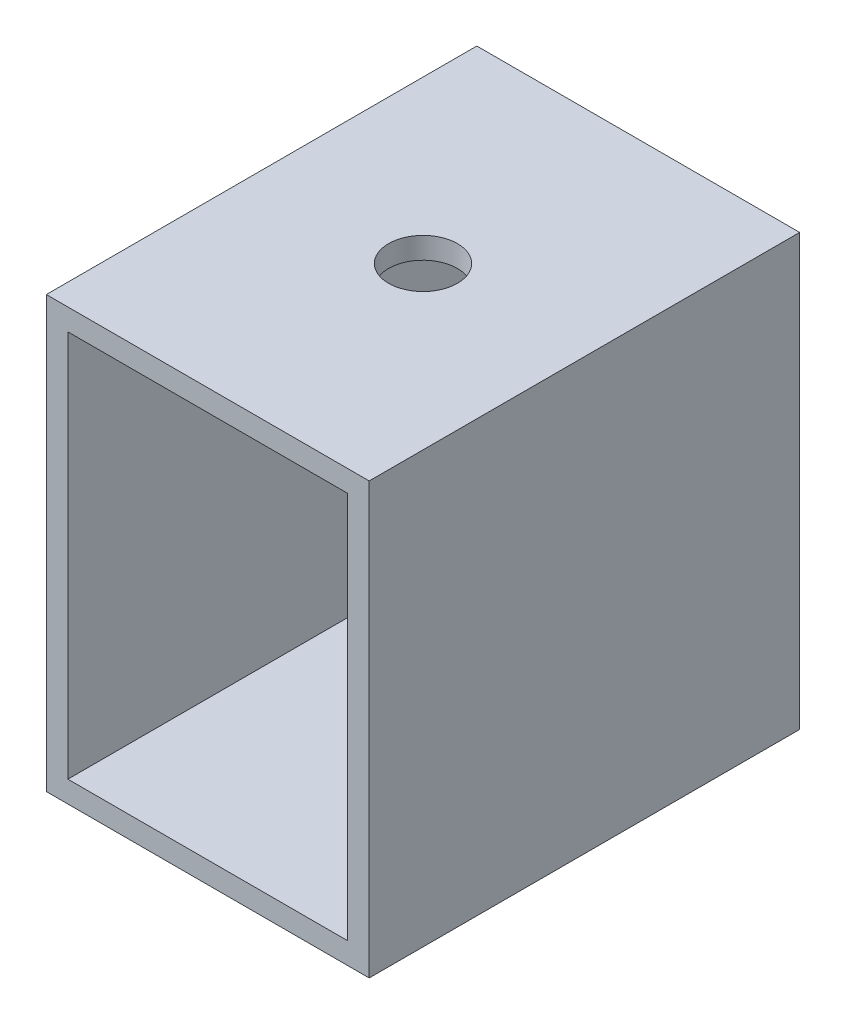
SolidWorks part; units mm, degrees
material "1060 合金"
ref_plane "前视基准面" through (0, 0, 0) normal (0, 0, 1) x (1, 0, 0)
ref_plane "上视基准面" through (0, 0, 0) normal (0, 1, 0) x (1, 0, 0)
ref_plane "右视基准面" through (0, 0, 0) normal (1, 0, 0) x (0, 0, -1)
other "Configuration Table"
sketch "草图1" plane through (0, 0, 0) normal (0, 0, 1) x (1, 0, 0)
  line L1 (0, 0) -> (15, 0)
  line L2 (0, 0) -> (0, -20)
  line L3 (0, -20) -> (15, -20)
  line L4 (15, 0) -> (15, -20)
  dimension "D1" = 20
  dimension "D2" = 15
extrude "拉伸-薄壁1" add sketch "草图1" along normal blind 20 thin thin type one direction reverse wall 1
sketch "草图2" plane through (0, -20, 0) normal (0, -1, 0) x (1, 0, 0)
  circle A1 centre (7.5, 825) radius 2.6
  circle A2 centre (7.5, 825) radius 2.6
  dimension "D1" = 0
extrude "切除-拉伸1" [suppressed] cut sketch "草图2" against normal up to next
sketch "草图3" plane through (0, -20, 0) normal (0, -1, 0) x (1, 0, 0)
  line L0 (15, 20) -> (15, 0) construction
  line L1 (0, 20) -> (15, 20) construction
  circle A0 centre (7.5, 10) radius 1.6
  dimension "D3" = 3.2
  dimension "D1" = 7.5
  dimension "D2" = 10
extrude "切除-拉伸2" cut sketch "草图3" against normal through all
